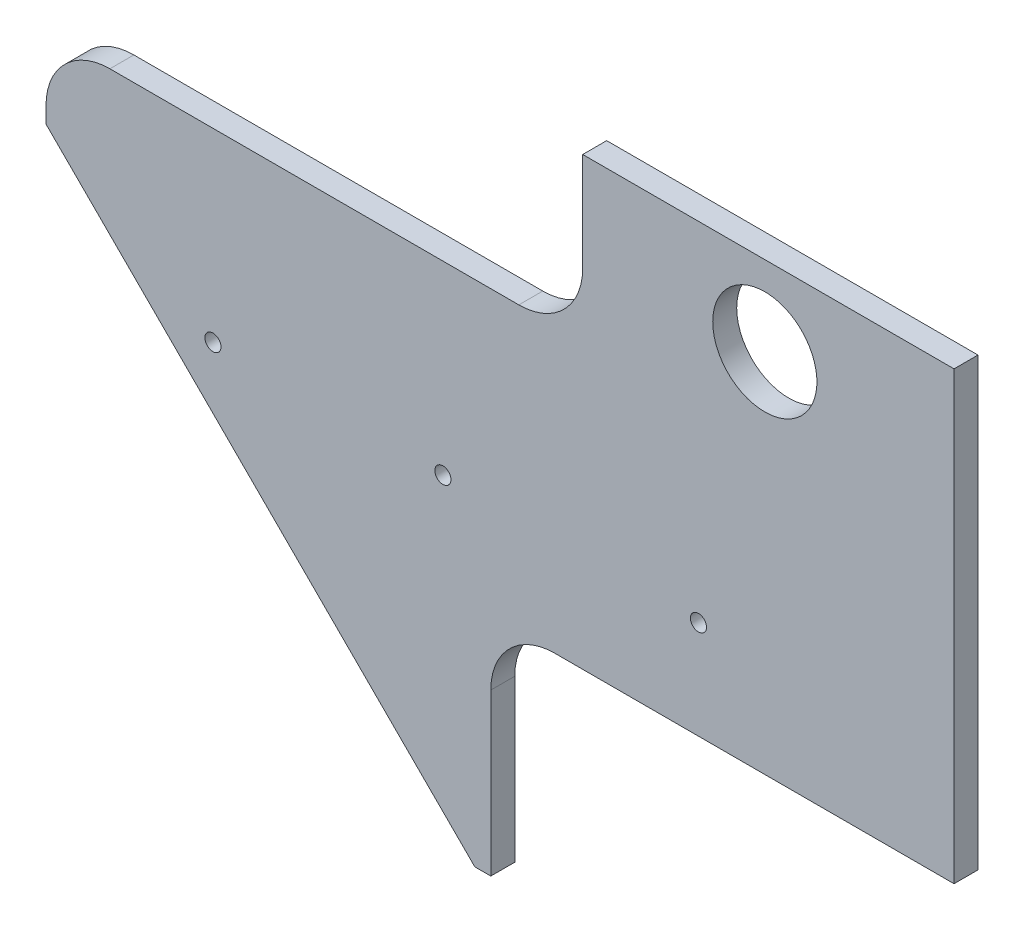
SolidWorks part; units mm, degrees
ref_plane "Front Plane" through (0, 0, 0) normal (0, 0, 1) x (1, 0, 0)
ref_plane "Top Plane" through (0, 0, 0) normal (0, 1, 0) x (1, 0, 0)
ref_plane "Right Plane" through (0, 0, 0) normal (1, 0, 0) x (0, 0, -1)
sketch "Sketch1" plane through (0, 0, 0) normal (0, 0, 1) x (1, 0, 0)
  line L0 (-138.2594, 48.9915) -> (32.2106, -121.4785)
  line L1 (32.2106, -121.4785) -> (222.7106, -121.4785)
  line L2 (-138.2594, 146.2068) -> (-138.2594, 48.9915)
  line L3 (-138.2594, 146.2068) -> (222.7106, 146.2068)
  line L4 (222.7106, -121.4785) -> (222.7106, 146.2068)
  circle A0 centre (147.4906, 113.4715) radius 20.701
  circle A2 centre (147.4906, 113.4715) radius 69.85 construction
  circle A3 centre (147.4906, 113.4715) radius 285.75 construction
  point P0 (0, 0)
  point P2 (147.4906, 113.4715)
  dimension "D4" = 234.95
  dimension "D1" = 45
  dimension "D2" = 267.6854
  dimension "D5" = 247.65
extrude "Boss-Extrude1" add sketch "Sketch1" along normal blind 9.525
sketch "Sketch2" plane through (0, 0, 9.525) normal (0, 0, 1) x (1, 0, 0)
  line L0 (32.2106, -121.4785) -> (222.7106, -121.4785) construction
  line L1 (222.7106, -121.4785) -> (38.5606, -121.4785)
  line L2 (222.7106, -121.4785) -> (222.7106, -32.0424)
  line L3 (222.7106, -32.0424) -> (38.5606, -32.0424)
  line L4 (38.5606, -121.4785) -> (38.5606, -32.0424)
extrude "Cut-Extrude1" cut sketch "Sketch2" against normal through all contours L3 L4 L1 L2
fillet "Fillet1" radius 25.4 1 edges at (38.5606, -32.0424, 4.7625)
sketch "Sketch4" plane through (0, 0, 9.525) normal (0, 0, 1) x (1, 0, 0)
  line L1 (-138.2594, 146.2068) -> (-138.2594, 48.9915) construction
  line L3 (-138.2594, 146.2068) -> (75.1006, 146.2068)
  line L4 (-138.2594, 146.2068) -> (-138.2594, 80.7415)
  line L5 (-138.2594, 80.7415) -> (75.1006, 80.7415)
  line L6 (75.1006, 146.2068) -> (75.1006, 80.7415)
extrude "Cut-Extrude2" cut sketch "Sketch4" against normal through all contours L5 L6 L3 L4
fillet "Fillet2" radius 25.4 2 edges at (-138.2594, 80.7415, 4.7625) (75.1006, 80.7415, 4.7625)
hole_wizard "Ø6.4 (6.4) Diameter Hole2" positions "Sketch15" profile "Sketch14" hole size "Ø6.4" standard "Lanco STD" end condition through all
sketch "Sketch15" plane through (0, 0, 0) normal (0, 0, -1) x (-1, 0, 0)
  point P3 (-121.1106, 7.0429)
  point P6 (-19.5106, 7.0429)
  point P9 (71.8957, 7.0429)
sketch "Sketch14" plane through (121.1106, 7.0429, 0) normal (1, 0, 0) x (0, 1, 0)
  line L0 (0, 0) -> (0, 9.525)
  line L1 (0, 9.525) -> (3.2, 9.525)
  line L2 (3.2, 9.525) -> (3.2, 0)
  line L5 (3.2, 0) -> (0, 0)
  line L11 (0, -6.35) -> (0, 107.95) construction
  dimension "Thru Hole Dia." = 6.4
  dimension "Thru Hole Depth" = 9.525
sketch "Sketch16" plane through (222.7106, 0, 0) normal (1, 0, 0) x (0, 0, -1)
  line L0 (0, -32.0424) -> (0, 146.2068) construction
  line L1 (-9.525, 146.2068) -> (0, 146.2068)
  line L2 (-9.525, 146.2068) -> (-9.525, 145.2215)
  line L3 (-9.525, 145.2215) -> (0, 145.2215)
  line L4 (0, 146.2068) -> (0, 145.2215)
extrude "Cut-Extrude3" cut sketch "Sketch16" against normal through all
